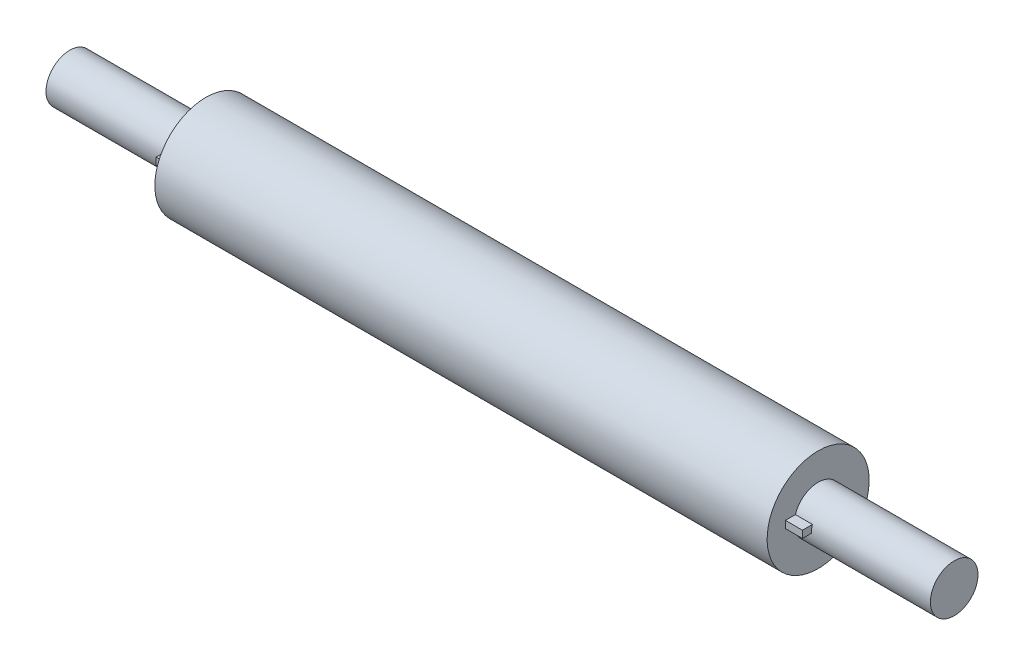
SolidWorks part; units mm, degrees
material "Nylon 101"
ref_plane "Front Plane" through (0, 0, 0) normal (0, 0, 1) x (1, 0, 0)
ref_plane "Top Plane" through (0, 0, 0) normal (0, 1, 0) x (1, 0, 0)
ref_plane "Right Plane" through (0, 0, 0) normal (1, 0, 0) x (0, 0, -1)
sketch "Sketch2" plane through (0, 0, 0) normal (0, 0, 1) x (1, 0, 0)
  line L0 (130, 0) -> (-130, 0)
  line L2 (-90, -7) -> (-90, -15)
  line L3 (-90, -15) -> (90, -15)
  line L4 (90, -7) -> (90, -15)
  line L7 (90, -7) -> (130, -7)
  line L8 (130, 0) -> (130, -7)
  line L11 (-90, -7) -> (-130, -7)
  line L12 (-130, 0) -> (-130, -7)
  dimension "D1" = 180
  dimension "D2" = 7
  dimension "D3" = 15
  dimension "D4" = 90
  dimension "D5" = 40
  dimension "D6" = 7
  dimension "D7" = 40
  dimension "D8" = 7
revolve "Revolve1" add sketch "Sketch2" angle 360 about L0
ref_axis "Axis1" through (-90, 0, 0) along (1, 0, 0)
sketch "Sketch3" plane through (90, 0, 0) normal (1, 0, 0) x (0, 0, -1)
  line L0 (-7, 0) -> (-9.6119, 0)
  line L1 (-9.6119, 0) -> (-9.6119, 2.1033)
  line L2 (-9.6119, 2.1033) -> (-6.6765, 2.1033)
  arc A0 (-6.6765, 2.1033) -> (-7, 0) centre (0, 0) ccw
extrude "Boss-Extrude1" add sketch "Sketch3" along normal blind 5
mirror "Mirror1" about plane through (0, 0, 0) normal (1, 0, 0) of "Boss-Extrude1"
